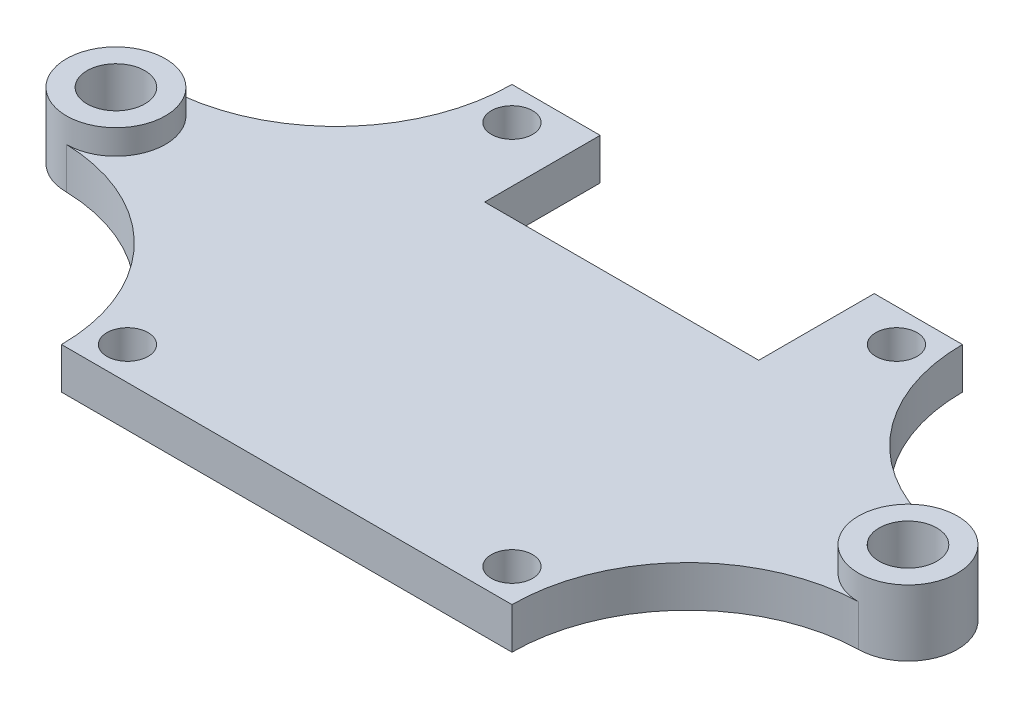
SolidWorks part; units mm, degrees
ref_plane "Front Plane" through (0, 0, 0) normal (0, 0, 1) x (1, 0, 0)
ref_plane "Top Plane" through (0, 0, 0) normal (0, 1, 0) x (1, 0, 0)
ref_plane "Right Plane" through (0, 0, 0) normal (1, 0, 0) x (0, 0, -1)
sketch "Sketch2" plane through (0, 0, 0) normal (0, 1, 0) x (1, 0, 0)
  line L1 (0, 0) -> (27.3, 0)
  line L2 (0, 0) -> (0, 27.3)
  line L3 (0, 27.3) -> (27.3, 27.3)
  line L4 (27.3, 0) -> (27.3, 27.3)
  line L5 (2, 25.3) -> (25.3, 25.3)
  line L6 (2, 25.3) -> (2, 2)
  line L7 (2, 2) -> (25.3, 2)
  line L8 (25.3, 25.3) -> (25.3, 2)
  line L9 (2, 25.3) -> (25.3, 2) construction
  line L10 (2, 2) -> (25.3, 25.3) construction
  circle A0 centre (2, 25.3) radius 1.25
  circle A1 centre (25.3, 25.3) radius 1.25
  circle A2 centre (25.3, 2) radius 1.25
  circle A3 centre (2, 2) radius 1.25
  circle A4 centre (-10.35, 13.65) radius 1.75
  circle A5 centre (37.65, 13.65) radius 1.75
  circle A6 centre (-10.35, 13.65) radius 3
  circle A7 centre (37.65, 13.65) radius 3
  arc A8 (0, 27.3) -> (-10.35, 16.65) centre (-10.6543, 27.3) cw
  arc A9 (0, 0) -> (-10.35, 10.65) centre (-10.6543, 0) ccw
  arc A10 (27.3, 27.3) -> (37.65, 16.65) centre (37.9543, 27.3) ccw
  arc A11 (27.3, 0) -> (37.65, 10.65) centre (37.9543, 0) cw
  point P5 (13.65, 13.65)
  dimension "D1" = 27.3
  dimension "D2" = 27.3
  dimension "D3" = 23.3
  dimension "D4" = 23.3
  dimension "D5" = 2
  dimension "D6" = 2
extrude "Boss-Extrude1" add sketch "Sketch2" along normal blind 2.5 contours L1 L4 L3 L2 A3 L6 A0 L5 A1 L8 A2 L7 | A3 L7 A2 L8 A1 L5 A0 L6 | A9 L2 A8 A6 | L4 A11 A7 A10 region at (0.3861, 0, -13.65) region at (-3.194, 0, -13.65) region at (30.494, 0, -13.65) region at (13.65, 0, -13.65)
extrude "Boss-Extrude2" add sketch "Sketch2<4>" along normal blind 4 contours A6 A4 | A7 A5 region at (-13.2651, 0, -13.65) region at (34.7349, 0, -13.65)
sketch "Sketch2<4>" plane through (0, 0, 0) normal (0, 1, 0) x (1, 0, 0) same geometry as "Sketch2"
sketch "Sketch3" plane through (0, 2.5, 0) normal (0, 1, 0) x (1, 0, 0)
  line L0 (0, 27.3) -> (27.3, 27.3) construction
  line L1 (5.3457, 27.3) -> (21.9543, 27.3)
  line L2 (5.3457, 27.3) -> (5.3457, 20.3)
  line L3 (5.3457, 20.3) -> (21.9543, 20.3)
  line L4 (21.9543, 27.3) -> (21.9543, 20.3)
  arc A0 (-10.35, 16.65) -> (0, 27.3) centre (-10.6543, 27.3) ccw construction
  arc A1 (27.3, 27.3) -> (37.65, 16.65) centre (37.9543, 27.3) ccw construction
  dimension "D1" = 16
  dimension "D2" = 16
  dimension "D3" = 7
extrude "Cut-Extrude1" cut sketch "Sketch3" against normal blind 3.25
